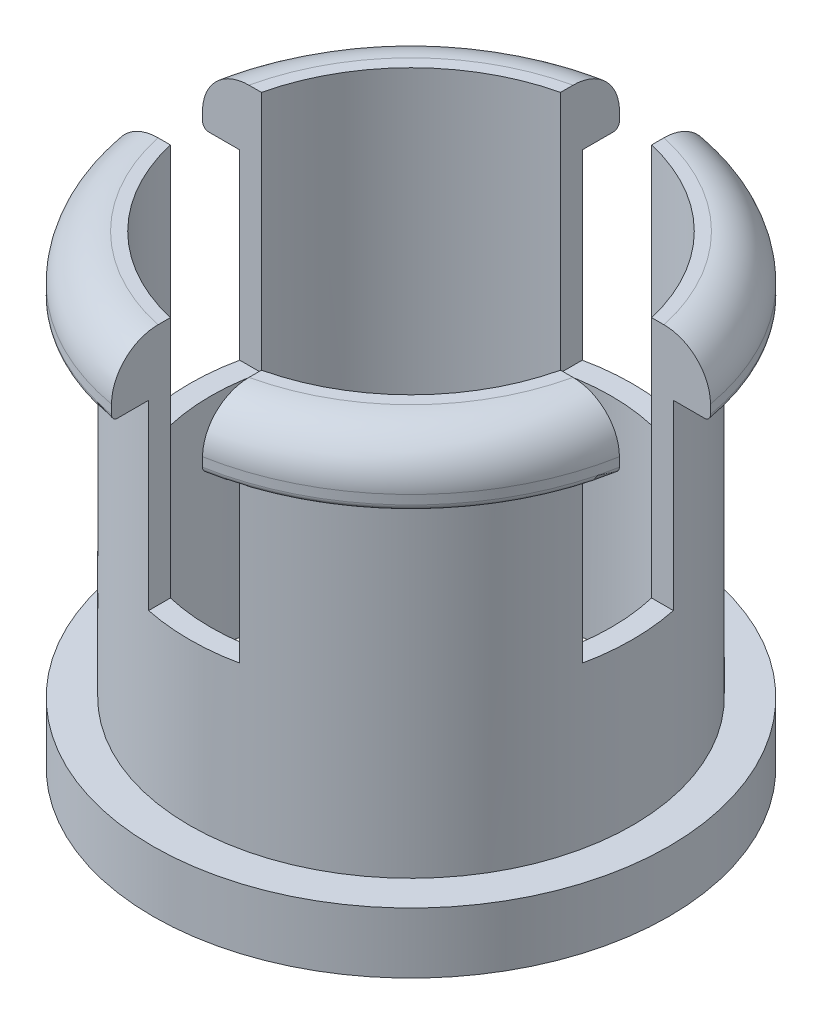
SolidWorks part; units mm, degrees
ref_plane "Front Plane" through (0, 0, 0) normal (0, 0, 1) x (1, 0, 0)
ref_plane "Top Plane" through (0, 0, 0) normal (0, 1, 0) x (1, 0, 0)
ref_plane "Right Plane" through (0, 0, 0) normal (1, 0, 0) x (0, 0, -1)
sketch "Sketch1" plane through (0, 0, 0) normal (0, 1, 0) x (1, 0, 0)
  line L1 (-9, 1.5) -> (9, 1.5)
  line L2 (-9, 1.5) -> (-9, -1.5)
  line L3 (-9, -1.5) -> (9, -1.5)
  line L4 (9, 1.5) -> (9, -1.5)
  line L5 (-9, 1.5) -> (9, -1.5) construction
  line L6 (-9, -1.5) -> (9, 1.5) construction
  circle A0 centre (0, 0) radius 7.3
  circle A1 centre (0, 0) radius 6.6
  circle A2 centre (0, 0) radius 8.5
  dimension "D1" = 14.6
  dimension "D2" = 13.2
  dimension "D3" = 17
  dimension "D4" = 18
  dimension "D5" = 3
extrude "Boss-Extrude1" add sketch "Sketch1" along normal blind 11.3 contours L3 A1 | L3 A1 L1 | L1 A1 | A0 region at (0, 0, -3.6275) region at (0, 0, 0) region at (0, 0, 3.6275)
extrude "Boss-Extrude2" add sketch "Sketch1<3>" against normal blind 2 contours L1 A1 | L3 A1 L1 | L3 A1 | A2 region at (0, 0, -3.6275) region at (0, 0, 0) region at (0, 0, 3.6275)
sketch "Sketch1<3>" plane through (0, 0, 0) normal (0, 1, 0) x (1, 0, 0) same geometry as "Sketch1"
extrude "Boss-Extrude3" add sketch "Sketch1<4>" along normal blind 2 from surface contours L3 A1 | L3 A1 L1 | L1 A1 | A2 region at (0, 0, -3.6275) region at (0, 0, 0) region at (0, 0, 3.6275) starting at face at (0, 11.3, 7.3)
sketch "Sketch1<4>" plane through (0, 0, 0) normal (0, 1, 0) x (1, 0, 0) same geometry as "Sketch1"
fillet "Fillet1" radius 1.5 1 edges at (0, 13.3, 8.5)
fillet "Fillet2" radius 0.2 1 edges at (0, 11.3, 8.5)
extrude "Cut-Extrude1" cut sketch "Sketch1<6>" against normal blind 8 from surface contours L2 L3 L4 L1 starting at face at (0, 13.3, 7)
sketch "Sketch1<6>" plane through (0, 0, 0) normal (0, 1, 0) x (1, 0, 0) same geometry as "Sketch1"
sketch "Sketch3" plane through (0, 0, 0) normal (0, 1, 0) x (1, 0, 0)
  line L1 (-1.5, 11.3257) -> (1.5, 11.3257)
  line L2 (-1.5, 11.3257) -> (-1.5, -11.3257)
  line L3 (-1.5, -11.3257) -> (1.5, -11.3257)
  line L4 (1.5, 11.3257) -> (1.5, -11.3257)
  line L5 (-1.5, 11.3257) -> (1.5, -11.3257) construction
  line L6 (-1.5, -11.3257) -> (1.5, 11.3257) construction
  point P0 (0, 0)
  dimension "D1" = 3
extrude "Cut-Extrude3" cut sketch "Sketch3" against normal up to surface (-5.3 mm away) from surface up to face at (6.8679, 5.3, 0) starting at face at (0, 13.3, -4.15)
